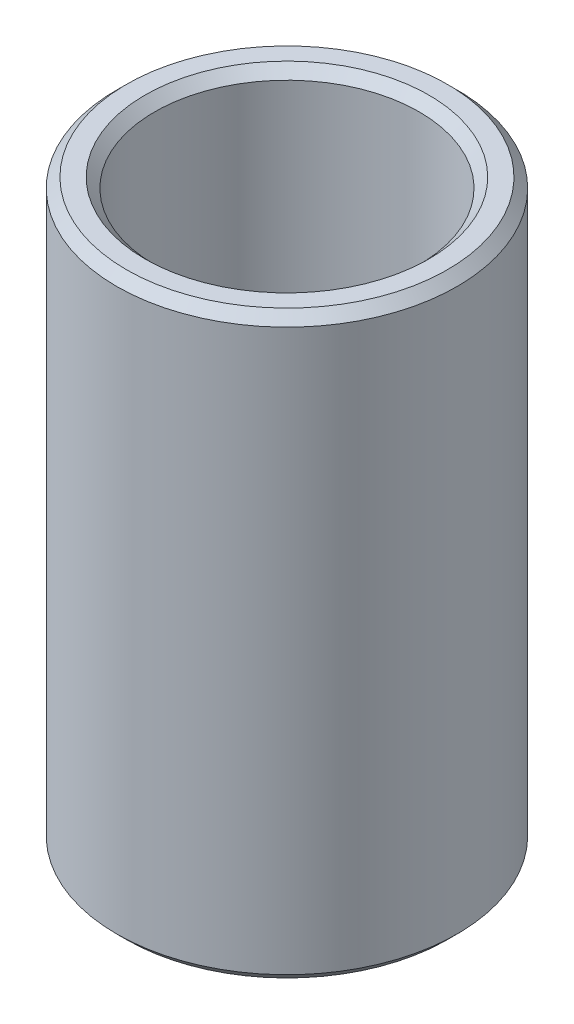
SolidWorks part; units mm, degrees
ref_plane "Front Plane" through (0, 0, 0) normal (0, 0, 1) x (1, 0, 0)
ref_plane "Top Plane" through (0, 0, 0) normal (0, 1, 0) x (1, 0, 0)
ref_plane "Right Plane" through (0, 0, 0) normal (1, 0, 0) x (0, 0, -1)
sketch "Sketch1" plane through (0, 0, 0) normal (0, 1, 0) x (1, 0, 0)
  circle A0 centre (0, 0) radius 30
  dimension "SLEEVE_OD" = 60
extrude "Boss-Extrude1" add sketch "Sketch1" along normal blind 102.24
sketch "Sketch2" plane through (0, 0, 0) normal (0, 1, 0) x (1, 0, 0)
  circle A0 centre (0, 0) radius 23.3153
  dimension "BORE_D" = 46.6306
extrude "Cut-Extrude1" cut sketch "Sketch2" along normal through all
chamfer "Chamfer1" distance 1.7064 angle 45 4 edges at (0, 102.24, 23.3153) (0, 0, 23.3153) (0, 0, 30) (0, 102.24, 30)
